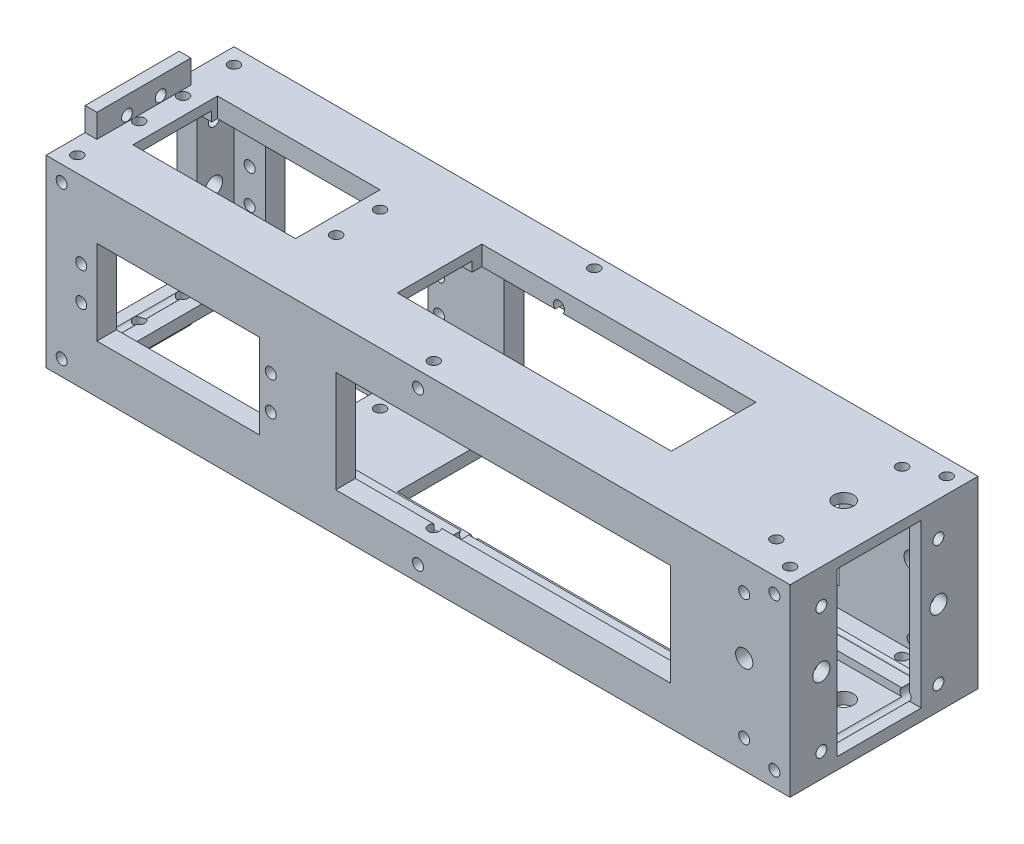
SolidWorks part; units mm, degrees
material "ABS"
ref_plane "Plano frontal" through (0, 0, 0) normal (0, 0, 1) x (1, 0, 0)
ref_plane "Plano superior" through (0, 0, 0) normal (0, 1, 0) x (1, 0, 0)
ref_plane "Plano direito" through (0, 0, 0) normal (1, 0, 0) x (0, 0, -1)
sketch "Esboço1" plane through (0, 0, 0) normal (0, 0, 1) x (1, 0, 0)
  line L1 (0, 0) -> (190, 0)
  line L2 (0, 0) -> (0, 47)
  line L3 (0, 47) -> (190, 47)
  line L4 (190, 0) -> (190, 47)
  dimension "D1" = 190
  dimension "D2" = 47
extrude "Ressalto-extrusão1" add sketch "Esboço1" along normal blind 46 and the other way blind 2
sketch "Esboço2" plane through (0, 0, 0) normal (1, 0, 0) x (0, 0, -1)
  line L1 (-41, 42) -> (-3, 42)
  line L2 (-41, 42) -> (-41, 5)
  line L3 (-41, 5) -> (-3, 5)
  line L4 (-3, 42) -> (-3, 5)
  dimension "D1" = 5
  dimension "D2" = 5
  dimension "D3" = 5
  dimension "D4" = 5
extrude "Corte-extrusão1" cut sketch "Esboço2" along normal through all
sketch "Esboço3" plane through (0, 0, 0) normal (0, 0, 1) x (1, 0, 0)
  line L1 (54.5, 34) -> (13, 34)
  line L2 (54.5, 34) -> (54.5, 12.4)
  line L3 (54.5, 12.4) -> (13, 12.4)
  line L4 (13, 34) -> (13, 12.4)
  circle A0 centre (205.6134, 31.5003) radius 1.25
  circle A1 centre (9, 27.5) radius 1.4
  circle A2 centre (9, 18.9) radius 1.4
  circle A3 centre (57.4, 27.5) radius 1.4
  circle A4 centre (57.4, 18.9) radius 1.4
  dimension "D6" = 2.8
  dimension "D1" = 13
  dimension "D2" = 21.6
  dimension "D3" = 13
  dimension "D4" = 41.5
  dimension "D7" = 2
  dimension "D8" = 6.5
  dimension "D10" = 6.5
  dimension "D11" = 4
  dimension "D12" = 4
  dimension "D13" = 2
extrude "Corte-extrusão6" cut sketch "Esboço3" along normal through all and the other way through all
sketch "Esboço8" plane through (0, 0, 0) normal (1, 0, 0) x (0, 0, -1)
  line L1 (2, 47) -> (-46, 47)
  line L2 (2, 47) -> (2, 0)
  line L3 (2, 0) -> (-46, 0)
  line L4 (-46, 47) -> (-46, 0)
sketch "Esboço11" plane through (0, 0, 0) normal (0, 0, 1) x (1, 0, 0)
  line L0 (0, 0) -> (190, 0) construction
  line L1 (190, 47) -> (187, 47)
  line L2 (190, 47) -> (190, 0)
  line L3 (190, 0) -> (187, 0)
  line L4 (187, 47) -> (187, 0)
  dimension "D1" = 3
extrude "Ressalto-extrusão4" add sketch "Esboço11" along normal through all
extrude "Ressalto-extrusão5" add sketch "Esboço8" along normal blind 5
sketch "Esboço12" plane through (0, 0, 0) normal (1, 0, 0) x (0, 0, -1)
  line L0 (-12.5, 44.5) -> (-34, 44.5)
  line L1 (-12.5, 44.5) -> (-12.5, 3)
  line L2 (-12.5, 3) -> (-34, 3)
  line L3 (-34, 44.5) -> (-34, 3)
  dimension "D1" = 21.5
  dimension "D2" = 41.5
  dimension "D3" = 12
  dimension "D4" = 3
extrude "Corte-extrusão8" cut sketch "Esboço12" along normal through all
sketch "Esboço13" plane through (0, 47, 0) normal (0, 1, 0) x (1, 0, 0)
  line L0 (190, 2) -> (190, -46) construction
  circle A0 centre (178.2104, -5.6) radius 1.4
  circle A1 centre (178.2104, -37.7) radius 1.4
  dimension "D1" = 2.8
  dimension "D2" = 11.7896
  dimension "D4" = 7.6
  dimension "D3" = 2
extrude "Corte-extrusão10" cut sketch "Esboço13" against normal through all
sketch "Esboço14" plane through (0, 47, 0) normal (0, 1, 0) x (1, 0, 0)
  circle A0 centre (178.2104, -20.5) radius 2.5
  circle A1 centre (178.2104, -5.6) radius 1.4 construction
  dimension "D1" = 14.9
  dimension "D2" = 5
  dimension "D3" = 0
extrude "Corte-extrusão12" cut sketch "Esboço14" against normal through all
sketch "Esboço16" plane through (0, 0, 0) normal (0, 0, 1) x (1, 0, 0)
  line L0 (190, 0) -> (190, 47) construction
  circle A0 centre (178.3, 39.4037) radius 1.4
  circle A1 centre (178.3, 7.3037) radius 1.4
  circle A2 centre (178.3, 24.9086) radius 2.2
  dimension "D4" = 4.4
  dimension "D1" = 11.7
  dimension "D2" = 11.7
  dimension "D3" = 32.1
extrude "Corte-extrusão14" cut sketch "Esboço16" against normal through all and the other way through all
sketch "Esboço17" plane through (190, 0, 0) normal (1, 0, 0) x (0, 0, -1)
  circle A0 centre (-38, 38.2451) radius 1.4
  circle A1 centre (-38, 6.1451) radius 1.4
  circle A2 centre (-38, 23.75) radius 2.2
  circle A3 centre (-8.1067, 38.2451) radius 1.4
  circle A4 centre (-8.1067, 23.75) radius 2.2
  circle A5 centre (-8.1067, 6.1451) radius 1.4
  dimension "D7" = 0
  dimension "D6" = 2
extrude "Corte-extrusão15" cut sketch "Esboço17" against normal through all and the other way blind 194
sketch "Esboço18" plane through (0, 0, 0) normal (0, 0, 1) x (1, 0, 0)
  line L0 (0, 0) -> (190, 0) construction
  line L1 (74.0081, 36) -> (159.4435, 36)
  line L2 (74.0081, 36) -> (74.0081, 10)
  line L3 (74.0081, 10) -> (159.4435, 10)
  line L4 (159.4435, 36) -> (159.4435, 10)
  point P4 (95, 0)
  dimension "D1" = 26
  dimension "D2" = 10
extrude "Corte-extrusão16" cut sketch "Esboço18" against normal through all and the other way through all
sketch "Esboço5" plane through (0, 0, 0) normal (0, 1, 0) x (1, 0, 0)
  line L0 (50.3, -11) -> (8.8, -11)
  line L1 (50.3, -11) -> (50.3, -32.6)
  line L2 (50.3, -32.6) -> (8.8, -32.6)
  line L3 (8.8, -11) -> (8.8, -32.6)
  line L4 (145.3, -10) -> (75.3, -10)
  line L5 (145.3, -10) -> (145.3, -31.6)
  line L6 (145.3, -31.6) -> (75.3, -31.6)
  line L7 (75.3, -10) -> (75.3, -31.6)
  line L8 (0, -46) -> (0, 2) construction
  line L9 (190, 2) -> (0, 2) construction
  circle A0 centre (219.6346, -28.0756) radius 1.25
  circle A1 centre (4.4, -15.4) radius 1.4
  circle A2 centre (4.4, -26.6) radius 1.4
  circle A3 centre (54.7, -15.4) radius 1.4
  circle A4 centre (54.7, -26.6) radius 1.4
  dimension "D1" = 4.4
  dimension "D2" = 4.4
  dimension "D3" = 4.4
  dimension "D4" = 13
  dimension "D5" = 25
  dimension "D6" = 12
  dimension "D7" = 21.6
  dimension "D8" = 21.6
  dimension "D9" = 4.4
  dimension "D10" = 0
  dimension "D11" = 11.2
  dimension "D12" = 0
  dimension "D13" = 4.4
  dimension "D14" = 0
  dimension "D15" = 41.5
extrude "Corte-extrusão4" cut sketch "Esboço5" along normal through all
sketch "Esboço19" plane through (0, 0, 0) normal (0, 1, 0) x (1, 0, 0)
  line L2 (190, -46) -> (0, -46) construction
  line L3 (0, 2) -> (190, 2) construction
  circle A0 centre (4, -2) radius 1.4
  circle A1 centre (4, -42) radius 1.4
  circle A2 centre (186, -2) radius 1.4
  circle A3 centre (186, -42) radius 1.4
  circle A4 centre (95, -42) radius 1.4
  circle A5 centre (95, -1) radius 1.4
  point P14 (95, -46)
  point P17 (95, -46)
  point P23 (95, 2)
  point P24 (95, 2)
  dimension "D1" = 4
  dimension "D2" = 4
  dimension "D3" = 4
  dimension "D4" = 4
  dimension "D5" = 4
  dimension "D6" = 4
  dimension "D7" = 4
  dimension "D8" = 4
  dimension "D9" = 0
  dimension "D10" = 4
  dimension "D11" = 0
  dimension "D12" = 3
extrude "Corte-extrusão17" cut sketch "Esboço19" against normal blind 74 and the other way through all
sketch "Esboço21" plane through (0, 0, 46) normal (0, 0, 1) x (1, 0, 0)
  line L0 (190, 47) -> (0, 47) construction
  line L1 (0, 0) -> (190, 0) construction
  circle A0 centre (4, 43) radius 1.4
  circle A1 centre (4, 4) radius 1.4
  circle A2 centre (186, 4) radius 1.4
  circle A3 centre (186, 43) radius 1.4
  circle A4 centre (95, 43) radius 1.4
  circle A5 centre (95, 4) radius 1.4
  point P15 (95, 47)
  point P18 (95, 47)
  point P21 (95, 0)
  point P24 (95, 0)
  dimension "D1" = 4
  dimension "D2" = 4
  dimension "D3" = 4
  dimension "D4" = 4
  dimension "D5" = 4
  dimension "D6" = 4
  dimension "D7" = 4
  dimension "D8" = 4
  dimension "D9" = 0
  dimension "D10" = 4
  dimension "D11" = 0
  dimension "D12" = 4
extrude "Corte-extrusão19" cut sketch "Esboço21" against normal blind 74 and the other way blind 74
sketch "Esboço22" plane through (0, 0, 0) normal (1, 0, 0) x (0, 0, -1)
  line L0 (2, 47) -> (-46, 47) construction
  line L1 (-36, 47) -> (-12, 47)
  line L2 (-36, 47) -> (-36, 53)
  line L3 (-36, 53) -> (-12, 53)
  line L4 (-12, 47) -> (-12, 53)
  line L5 (2, 0) -> (-46, 0) construction
  line L6 (-36, 0) -> (-12, 0)
  line L7 (-36, 0) -> (-36, -6)
  line L8 (-36, -6) -> (-12, -6)
  line L9 (-12, 0) -> (-12, -6)
  dimension "D1" = 24
  dimension "D2" = 6
  dimension "D3" = 6
  dimension "D4" = 24
  dimension "D5" = 10
  dimension "D6" = 10
extrude "Ressalto-extrusão6" add sketch "Esboço22" along normal blind 3
sketch "Esboço23" plane through (0, 0, 0) normal (1, 0, 0) x (0, 0, -1)
  circle A0 centre (-19.7, 48.5) radius 1.4
  circle A1 centre (-28.3, 48.5) radius 1.4
  circle A2 centre (-19.9, -1) radius 1.4
  circle A3 centre (-28.5, -1) radius 1.4
  dimension "D1" = 8.6
  dimension "D2" = 4
  dimension "D3" = 5.7
  dimension "D4" = 4
  dimension "D5" = 4
  dimension "D6" = 0
extrude "Corte-extrusão21" cut sketch "Esboço23" along normal blind 3
sketch "Esboço24" plane through (0, 0, 0) normal (0, 1, 0) x (1, 0, 0)
  line L0 (5.4, -42) -> (93.6, -42) construction
  circle A0 centre (95, -42) radius 1.4 construction
  text T0 "Robotinics rev 1.1 Maurinsoft.com"
extrude "Corte-extrusão22" cut sketch "Esboço24" along normal blind 2
